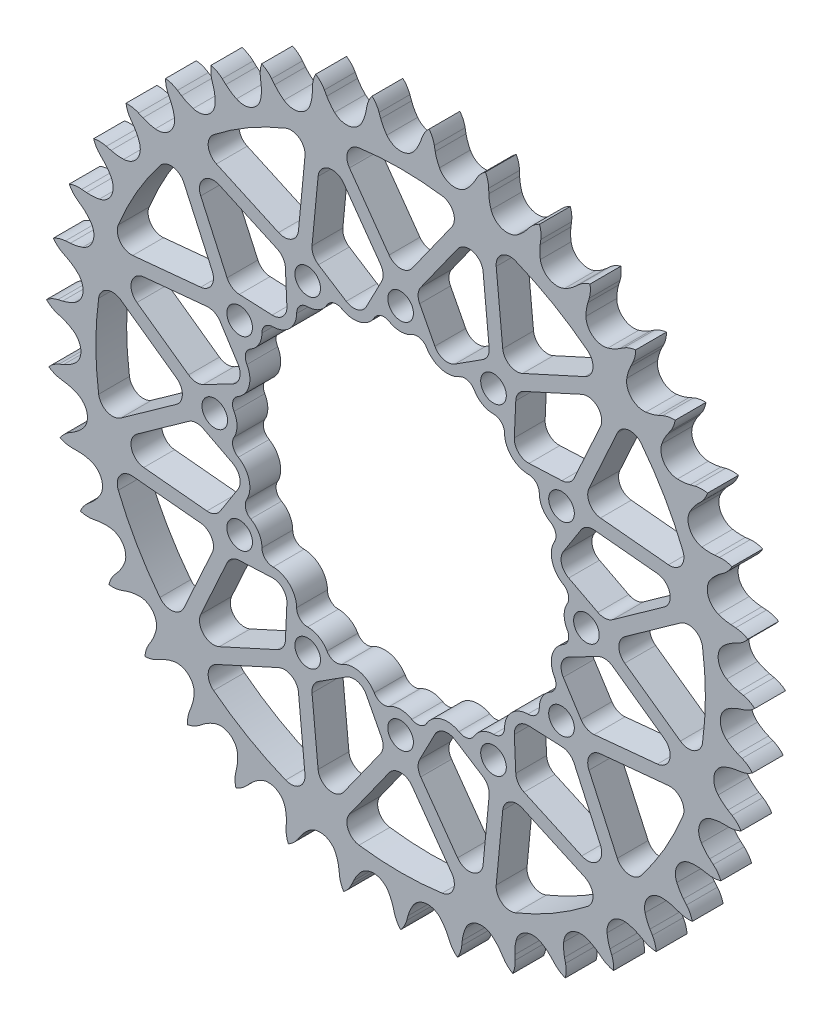
SolidWorks part; units mm, degrees
material "7075-T6 (SN)"
ref_plane "Front Plane" through (0, 0, 0) normal (0, 0, 1) x (1, 0, 0)
ref_plane "Top Plane" through (0, 0, 0) normal (0, 1, 0) x (1, 0, 0)
ref_plane "Right Plane" through (0, 0, 0) normal (1, 0, 0) x (0, 0, -1)
sketch "Work Sketch" plane through (0, 0, 0) normal (0, 0, 1) x (1, 0, 0)
  line L0 (0, 0) -> (0, 160.4542) construction
  line L1 (-112.0919, 78.9148) -> (87.2579, 78.9148) construction
  line L2 (5.102, 120.8822) -> (5.102, 112.9699) construction
  line L3 (-12.8497, 82.6953) -> (16.7256, 82.6953) construction
  line L4 (5.102, 82.6953) -> (-6.0879, 74.4036) construction
  line L5 (5.102, 82.6953) -> (-4.6505, 79.1506) construction
  line L6 (-4.6505, 79.1506) -> (-6.8863, 85.3019)
  line L7 (-11.5114, 78.0206) -> (-7.1525, 78.0206) construction
  line L8 (-11.0765, 124.7602) -> (-11.0765, 110.2345) construction
  line L9 (0, 0) -> (-3.4402, 42.6146) construction
  circle A0 centre (0, 0) radius 78.9148
  circle A1 centre (0, 78.9148) radius 4.0088
  arc A2 (-4.6505, 79.1506) -> (-3.2209, 76.5281) centre (5.0804, 82.7541) ccw
  circle A3 centre (-11.0765, 78.0206) radius 6.4254
  point P23 (-3.2209, 76.5281)
  dimension "D1" = 157.8295
  dimension "D8" = 10.3767
  dimension "D2" = 8.0177
  dimension "D3" = 5.102
  dimension "D4" = 3.7806
  dimension "D5" = 36.538
  dimension "D6" = 16.564
  dimension "D7" = 10.3767
  dimension "D9" = 0.8942
  dimension "D10" = 11.0765
  dimension "D11" = 4.615
sketch "Teeth Sketch" plane through (0, 0, 0) normal (0, 0, 1) x (1, 0, 0)
  line L0 (5.0376, 80.2155) -> (4.6505, 79.1506)
  line L1 (-7.4865, 92.7372) -> (-4.7839, 59.2593) construction
  line L2 (0, 0) -> (-10.9133, 132.3061) construction
  line L3 (7.8951, 79.9848) -> (8.1063, 78.8717)
  line L4 (16093.3137, -199351.4616) -> (-16096.7539, 199394.0762) construction
  line L5 (0, 146.3285) -> (0, 56.9858) construction
  line L6 (17.8398, 78.3686) -> (17.287, 77.3797)
  line L7 (0, -200000) -> (0, 200160.4542) construction
  line L8 (20.6234, 77.6826) -> (20.6533, 76.5499)
  line L9 (-4.6505, 79.1506) -> (-6.8863, 85.3019) construction
  line L10 (44.1616, 67.154) -> (43.8313, 66.0702)
  line L11 (-5.0376, 80.2155) -> (-4.6505, 79.1506)
  line L12 (30.18, 74.4921) -> (29.4757, 73.6046)
  line L13 (32.8175, 73.3684) -> (32.6653, 72.2456)
  line L14 (41.7385, 68.6862) -> (40.901, 67.9232)
  line L15 (52.2161, 61.1014) -> (51.267, 60.4826)
  line L16 (54.362, 59.2003) -> (53.8621, 58.1836)
  line L17 (61.3413, 51.9341) -> (60.3052, 51.4756)
  line L18 (63.1544, 49.7134) -> (62.4979, 48.79)
  line L19 (68.8777, 41.4218) -> (67.7815, 41.1354)
  line L20 (70.3112, 38.939) -> (69.515, 38.1328)
  line L21 (74.6303, 29.8366) -> (73.5023, 29.7298)
  line L22 (75.6469, 27.156) -> (74.7318, 26.488)
  line L23 (78.45, 17.4787) -> (77.3195, 17.5542)
  line L24 (79.0234, 14.6698) -> (78.013, 14.1572)
  line L25 (80.2378, 4.6681) -> (79.1341, 4.9239)
  line L26 (80.3533, 1.8035) -> (79.2737, 1.4597)
  line L27 (79.9476, -8.2634) -> (78.8992, -7.8338)
  line L28 (79.602, -11.1094) -> (78.4813, -11.2756)
  line L29 (77.5867, -20.9809) -> (76.6208, -20.3887)
  line L30 (76.7891, -23.7346) -> (75.6562, -23.7189)
  line L31 (73.2164, -33.155) -> (72.358, -32.4155)
  line L32 (71.9874, -35.7451) -> (70.8717, -35.5478)
  line L33 (66.9499, -44.4704) -> (66.2212, -43.6028)
  line L34 (65.3213, -46.8298) -> (64.2517, -46.4561)
  line L35 (58.9493, -54.634) -> (58.3693, -53.6608)
  line L36 (56.9634, -56.7016) -> (55.9676, -56.1612)
  line L37 (49.422, -63.3827) -> (49.0056, -62.329)
  line L38 (47.1301, -65.1049) -> (46.2339, -64.4118)
  line L39 (38.6147, -70.4897) -> (38.3727, -69.3829)
  line L40 (36.0763, -71.822) -> (35.3028, -70.9941)
  line L41 (26.8073, -75.7712) -> (26.746, -74.6398)
  line L42 (24.088, -76.679) -> (23.4574, -75.7377)
  line L43 (14.3056, -79.0901) -> (14.4266, -77.9636)
  line L44 (11.4759, -79.55) -> (11.0044, -78.5198)
  line L45 (1.4334, -80.3607) -> (1.7335, -79.2682)
  line L46 (-1.4334, -80.3607) -> (-1.7335, -79.2682)
  line L47 (-11.4759, -79.55) -> (-11.0044, -78.5198)
  line L48 (-14.3056, -79.0901) -> (-14.4266, -77.9636)
  line L49 (-24.088, -76.679) -> (-23.4574, -75.7377)
  line L50 (-26.8073, -75.7712) -> (-26.746, -74.6398)
  line L51 (-36.0763, -71.822) -> (-35.3028, -70.9941)
  line L52 (-38.6147, -70.4897) -> (-38.3727, -69.3829)
  line L53 (-47.1301, -65.1049) -> (-46.2339, -64.4118)
  line L54 (-49.422, -63.3827) -> (-49.0056, -62.329)
  line L55 (-56.9634, -56.7016) -> (-55.9676, -56.1612)
  line L56 (-58.9493, -54.634) -> (-58.3693, -53.6608)
  line L57 (-65.3213, -46.8298) -> (-64.2517, -46.4561)
  line L58 (-66.9499, -44.4704) -> (-66.2212, -43.6028)
  line L59 (-71.9874, -35.7451) -> (-70.8717, -35.5478)
  line L60 (-73.2164, -33.155) -> (-72.358, -32.4155)
  line L61 (-76.7891, -23.7346) -> (-75.6562, -23.7189)
  line L62 (-77.5867, -20.9809) -> (-76.6208, -20.3887)
  line L63 (-79.602, -11.1094) -> (-78.4813, -11.2756)
  line L64 (-79.9476, -8.2634) -> (-78.8992, -7.8338)
  line L65 (-80.3533, 1.8035) -> (-79.2737, 1.4597)
  line L66 (-80.2378, 4.6681) -> (-79.1341, 4.9239)
  line L67 (-79.0234, 14.6698) -> (-78.013, 14.1572)
  line L68 (-78.45, 17.4787) -> (-77.3195, 17.5542)
  line L69 (-75.6469, 27.156) -> (-74.7318, 26.488)
  line L70 (-74.6303, 29.8366) -> (-73.5023, 29.7298)
  line L71 (-70.3112, 38.939) -> (-69.515, 38.1328)
  line L72 (-68.8777, 41.4218) -> (-67.7815, 41.1354)
  line L73 (-63.1544, 49.7134) -> (-62.4979, 48.79)
  line L74 (-61.3413, 51.9341) -> (-60.3052, 51.4756)
  line L75 (-54.362, 59.2003) -> (-53.8621, 58.1836)
  line L76 (-52.2161, 61.1014) -> (-51.267, 60.4826)
  line L77 (-44.1616, 67.154) -> (-43.8313, 66.0702)
  line L78 (-41.7385, 68.6862) -> (-40.901, 67.9232)
  line L79 (-32.8175, 73.3684) -> (-32.6653, 72.2456)
  line L80 (-30.18, 74.4921) -> (-29.4757, 73.6046)
  line L81 (-20.6234, 77.6826) -> (-20.6533, 76.5499)
  line L82 (-17.8398, 78.3686) -> (-17.287, 77.3797)
  line L83 (-7.8951, 79.9848) -> (-8.1063, 78.8717)
  arc A0 (-6.8336, 82.8459) -> (-5.0376, 80.2155) centre (-11.0765, 78.0206) cw
  circle A1 centre (-11.0765, 78.0206) radius 6.4254 construction
  arc A2 (-3.2209, 76.5281) -> (-4.6505, 79.1506) centre (5.0804, 82.7541) cw
  arc A3 (-4.6505, 79.1506) -> (-3.2209, 76.5281) centre (5.0804, 82.7541) ccw construction
  circle A4 centre (0, 78.9148) radius 4.0088 construction
  arc A5 (-3.2209, 76.5281) -> (3.2209, 76.5281) centre (0, 78.9148) ccw
  arc A6 (3.2209, 76.5281) -> (4.6505, 79.1506) centre (-5.0804, 82.7541) ccw
  arc A7 (6.8336, 82.8459) -> (5.0376, 80.2155) centre (11.0765, 78.0206) ccw
  arc A8 (6.5443, 82.8692) -> (7.8951, 79.9848) centre (1.5824, 78.787) cw
  arc A9 (9.0967, 76.0537) -> (8.1063, 78.8717) centre (18.2893, 80.8676) cw
  arc A10 (9.0967, 76.0537) -> (15.4552, 75.0204) centre (12.6588, 77.8928) ccw
  arc A11 (15.4552, 75.0204) -> (17.287, 77.3797) centre (8.2601, 82.4975) ccw
  arc A12 (20.0345, 80.6769) -> (17.8398, 78.3686) centre (23.4484, 75.2334) ccw
  arc A13 (19.7528, 80.7463) -> (20.6234, 77.6826) centre (14.2002, 77.5129) cw
  arc A14 (21.1788, 73.6096) -> (20.6533, 76.5499) centre (31.0245, 76.8865) cw
  arc A15 (21.1788, 73.6096) -> (27.2892, 71.5697) centre (24.9898, 74.8535) ccw
  arc A16 (27.2892, 71.5697) -> (29.4757, 73.6046) centre (21.3867, 80.1041) ccw
  arc A17 (32.7165, 76.4184) -> (30.18, 74.4921) centre (35.2131, 70.4978) ccw
  arc A18 (32.4496, 76.5321) -> (32.8175, 73.3684) centre (26.4502, 74.2313) cw
  arc A19 (32.7124, 69.2591) -> (32.6653, 72.2456) centre (42.9562, 70.9142) cw
  arc A20 (32.7124, 69.2591) -> (38.4163, 66.2654) centre (36.6735, 69.8756) ccw
  arc A21 (38.4163, 66.2654) -> (40.901, 67.9232) centre (33.9593, 75.6361) ccw
  arc A22 (44.5512, 70.1807) -> (41.7385, 68.6862) centre (46.0657, 63.9363) ccw
  arc A23 (44.306, 70.3358) -> (44.1616, 67.154) centre (38.0153, 69.0271) cw
  arc A24 (43.3987, 63.1147) -> (43.8313, 66.0702) centre (53.7754, 63.1052) cw
  arc A25 (43.3987, 63.1147) -> (48.5486, 59.2448) centre (47.4074, 63.0878) ccw
  arc A26 (48.5486, 59.2448) -> (51.267, 60.4826) centre (45.6524, 69.2092) ccw
  arc A27 (55.2321, 62.1253) -> (52.2161, 61.1014) centre (55.7253, 55.7189) ccw
  arc A28 (55.0149, 62.3178) -> (54.362, 59.2003) centre (48.5957, 62.0351) cw
  arc A29 (52.961, 55.3358) -> (53.8621, 58.1836) centre (63.2018, 53.6618) cw
  arc A30 (52.961, 55.3358) -> (57.4234, 50.6899) centre (56.9135, 54.6662) ccw
  arc A31 (57.4234, 50.6899) -> (60.3052, 51.4756) centre (56.1632, 60.9898) ccw
  arc A32 (64.4824, 52.461) -> (61.3413, 51.9341) centre (63.9416, 46.0584) ccw
  arc A33 (64.2989, 52.6858) -> (63.1544, 49.7134) centre (57.9175, 53.4365) cw
  arc A34 (61.1517, 46.1237) -> (62.4979, 48.79) centre (70.9913, 42.8287) cw
  arc A35 (61.1517, 46.1237) -> (64.811, 40.8221) centre (64.9456, 44.8287) ccw
  arc A36 (64.811, 40.8221) -> (67.7815, 41.1354) centre (65.2193, 51.1908) ccw
  arc A37 (72.0627, 41.4379) -> (68.8777, 41.4218) centre (70.5018, 35.205) ccw
  arc A38 (71.9177, 41.6892) -> (70.3112, 38.939) centre (65.7393, 43.4539) cw
  arc A39 (67.7585, 35.717) -> (69.515, 38.1328) centre (76.9422, 30.8862) cw
  arc A40 (67.7585, 35.717) -> (70.5201, 29.8971) centre (71.2956, 33.8302) ccw
  arc A41 (70.5201, 29.8971) -> (73.5023, 29.7298) centre (72.5864, 40.0659) ccw
  arc A42 (77.7767, 29.3416) -> (74.6303, 29.8366) centre (75.2361, 23.4398) ccw
  arc A43 (77.6738, 29.6129) -> (75.6469, 27.156) centre (71.8585, 32.3458) cw
  arc A44 (72.6105, 24.3852) -> (74.7318, 26.488) centre (80.9003, 18.1439) cw
  arc A45 (72.6105, 24.3852) -> (74.4027, 18.1977) centre (75.7991, 21.9555) ccw
  arc A46 (74.4027, 18.1977) -> (77.3195, 17.5542) centre (78.0734, 27.9034) ccw
  arc A47 (81.4762, 16.4854) -> (78.45, 17.4787) centre (78.0218, 11.0675) ccw
  arc A48 (81.4182, 16.7697) -> (79.0234, 14.6698) centre (76.1166, 20.4) cw
  arc A49 (75.5818, 12.4219) -> (78.013, 14.1572) centre (82.7631, 4.9316) cw
  arc A50 (75.5818, 12.4219) -> (76.3583, 6.027) centre (78.3394, 9.5121) ccw
  arc A51 (76.3583, 6.027) -> (79.1341, 4.9239) centre (81.5384, 15.0182) ccw
  arc A52 (83.0656, 3.2022) -> (80.2378, 4.6681) centre (78.7868, -1.5914) ccw
  arc A53 (83.0539, 3.4922) -> (80.3533, 1.8035) centre (78.4033, 7.9259) cw
  arc A54 (76.5957, 0.1368) -> (79.2737, 1.4597) centre (82.4825, -8.4084) cw
  arc A55 (76.5957, 0.1368) -> (76.3363, -6.2998) centre (78.8508, -3.1776) ccw
  arc A56 (76.3363, -6.2998) -> (78.8992, -7.8338) centre (82.8916, 1.7441) ccw
  arc A57 (82.5035, -10.1639) -> (79.9476, -8.2634) centre (77.5113, -14.2091) ccw
  arc A58 (82.5385, -9.8758) -> (79.602, -11.1094) centre (78.6594, -4.7535) cw
  arc A59 (75.6257, -12.1517) -> (78.4813, -11.2756) centre (80.0655, -21.5307) cw
  arc A60 (75.6257, -12.1517) -> (74.3372, -18.4634) centre (77.3199, -15.785) ccw
  arc A61 (74.3372, -18.4634) -> (76.6208, -20.3887) centre (82.0979, -11.5753) ccw
  arc A62 (79.8047, -23.2668) -> (77.5867, -20.9809) centre (74.2283, -26.4587) ccw
  arc A63 (79.8855, -22.9881) -> (76.7891, -23.7346) centre (76.8783, -17.3098) cw
  arc A64 (72.6971, -24.1256) -> (75.6562, -23.7189) centre (75.5749, -34.0953) cw
  arc A65 (72.6971, -24.1256) -> (70.4128, -30.1488) centre (73.7866, -27.9836) ccw
  arc A66 (70.4128, -30.1488) -> (72.358, -32.4155) centre (79.178, -24.5948) ccw
  arc A67 (75.039, -35.7671) -> (73.2164, -33.155) centre (69.0227, -38.0232) ccw
  arc A68 (75.1634, -35.5049) -> (71.9874, -35.7451) centre (73.106, -29.4178) cw
  arc A69 (67.8857, -35.4746) -> (70.8717, -35.5478) centre (69.127, -45.7768) cw
  arc A70 (67.8857, -35.4746) -> (64.6648, -41.0534) centre (68.3422, -39.4574) ccw
  arc A71 (64.6648, -41.0534) -> (66.2212, -43.6028) centre (74.2074, -36.9773) ccw
  arc A72 (68.3299, -47.341) -> (66.9499, -44.4704) centre (62.0296, -48.6028) ccw
  arc A73 (68.4947, -47.1022) -> (65.3213, -46.8298) centre (67.4404, -40.7639) cw
  arc A74 (61.3161, -45.9049) -> (64.2517, -46.4561) centre (60.8887, -56.2728) cw
  arc A75 (61.3161, -45.9049) -> (57.2419, -50.8948) centre (61.1278, -49.9093) ccw
  arc A76 (57.2419, -50.8948) -> (58.3693, -53.6608) centre (67.3148, -48.4022) ccw
  arc A77 (59.851, -57.6888) -> (58.9493, -54.634) centre (53.4299, -57.9236) ccw
  arc A78 (60.052, -57.4796) -> (56.9634, -56.7016) centre (60.0281, -51.0542) cw
  arc A79 (53.1584, -55.1462) -> (55.9676, -56.1612) centre (51.0734, -65.3113) cw
  arc A80 (53.1584, -55.1462) -> (48.3366, -59.4179) centre (52.3302, -59.0685) ccw
  arc A81 (48.3366, -59.4179) -> (49.0056, -62.329) centre (58.6789, -58.5735) ccw
  arc A82 (49.822, -66.5425) -> (49.422, -63.3827) centre (43.4464, -65.7443) ccw
  arc A83 (50.054, -66.3682) -> (47.1301, -65.1049) centre (51.0611, -60.0222) cw
  arc A84 (43.6239, -62.9593) -> (46.2339, -64.4118) centre (39.9354, -72.6583) cw
  arc A85 (43.6239, -62.9593) -> (38.1793, -66.4022) centre (42.1772, -66.698) ccw
  arc A86 (38.1793, -66.4022) -> (38.3727, -69.3829) centre (48.5231, -67.2277) ccw
  arc A87 (38.5026, -73.6728) -> (38.6147, -70.4897) centre (32.3376, -71.8622) ccw
  arc A88 (38.7596, -73.538) -> (36.0763, -71.822) centre (40.7716, -67.4357) cw
  arc A89 (32.9596, -69.1417) -> (35.3028, -70.9941) centre (27.763, -78.1234) cw
  arc A90 (32.9596, -69.1417) -> (27.0333, -71.6667) centre (30.932, -72.6) ccw
  arc A91 (27.0333, -71.6667) -> (26.746, -74.6398) centre (37.1107, -74.1408) ccw
  arc A92 (26.1861, -78.8951) -> (26.8073, -75.7712) centre (20.3913, -76.1189) ccw
  arc A93 (26.4613, -78.8032) -> (24.088, -76.679) centre (29.4261, -73.1027) cw
  arc A94 (21.4417, -73.5335) -> (23.4574, -75.7377) centre (14.8716, -81.5653) cw
  arc A95 (21.4417, -73.5335) -> (15.187, -75.0751) centre (18.8855, -76.6216) ccw
  arc A96 (15.187, -75.0751) -> (14.4266, -77.9636) centre (24.7371, -79.1336) ccw
  arc A97 (13.1913, -82.0739) -> (14.3056, -79.0901) centre (7.9169, -78.4042) ccw
  arc A98 (13.4777, -82.0274) -> (11.4759, -79.55) centre (17.3186, -76.8763) cw
  arc A99 (9.3684, -76.0207) -> (11.0044, -78.5198) centre (1.595, -82.8946) cw
  arc A100 (9.3684, -76.0207) -> (2.9475, -76.5391) centre (6.35, -78.6589) ccw
  arc A101 (2.9475, -76.5391) -> (1.7335, -79.2682) centre (11.7228, -82.077) ccw
  arc A102 (-0.1451, -83.1271) -> (1.4334, -80.3607) centre (-4.7625, -78.6589) ccw
  arc A103 (0.1451, -83.1271) -> (-1.4334, -80.3607) centre (4.7625, -78.6589) cw
  arc A104 (-2.9475, -76.5391) -> (-1.7335, -79.2682) centre (-11.7228, -82.077) cw
  arc A105 (-2.9475, -76.5391) -> (-9.3684, -76.0207) centre (-6.35, -78.6589) ccw
  arc A106 (-9.3684, -76.0207) -> (-11.0044, -78.5198) centre (-1.595, -82.8946) ccw
  arc A107 (-13.4777, -82.0274) -> (-11.4759, -79.55) centre (-17.3186, -76.8763) ccw
  arc A108 (-13.1913, -82.0739) -> (-14.3056, -79.0901) centre (-7.9169, -78.4042) cw
  arc A109 (-15.187, -75.0751) -> (-14.4266, -77.9636) centre (-24.7371, -79.1336) cw
  arc A110 (-15.187, -75.0751) -> (-21.4417, -73.5335) centre (-18.8855, -76.6216) ccw
  arc A111 (-21.4417, -73.5335) -> (-23.4574, -75.7377) centre (-14.8716, -81.5653) ccw
  arc A112 (-26.4613, -78.8032) -> (-24.088, -76.679) centre (-29.4261, -73.1027) ccw
  arc A113 (-26.1861, -78.8951) -> (-26.8073, -75.7712) centre (-20.3913, -76.1189) cw
  arc A114 (-27.0333, -71.6667) -> (-26.746, -74.6398) centre (-37.1107, -74.1408) cw
  arc A115 (-27.0333, -71.6667) -> (-32.9596, -69.1417) centre (-30.932, -72.6) ccw
  arc A116 (-32.9596, -69.1417) -> (-35.3028, -70.9941) centre (-27.763, -78.1234) ccw
  arc A117 (-38.7596, -73.538) -> (-36.0763, -71.822) centre (-40.7716, -67.4357) ccw
  arc A118 (-38.5026, -73.6728) -> (-38.6147, -70.4897) centre (-32.3376, -71.8622) cw
  arc A119 (-38.1793, -66.4022) -> (-38.3727, -69.3829) centre (-48.5231, -67.2277) cw
  arc A120 (-38.1793, -66.4022) -> (-43.6239, -62.9593) centre (-42.1772, -66.698) ccw
  arc A121 (-43.6239, -62.9593) -> (-46.2339, -64.4118) centre (-39.9354, -72.6583) ccw
  arc A122 (-50.054, -66.3682) -> (-47.1301, -65.1049) centre (-51.0611, -60.0222) ccw
  arc A123 (-49.822, -66.5425) -> (-49.422, -63.3827) centre (-43.4464, -65.7443) cw
  arc A124 (-48.3366, -59.4179) -> (-49.0056, -62.329) centre (-58.6789, -58.5735) cw
  arc A125 (-48.3366, -59.4179) -> (-53.1584, -55.1462) centre (-52.3302, -59.0685) ccw
  arc A126 (-53.1584, -55.1462) -> (-55.9676, -56.1612) centre (-51.0734, -65.3113) ccw
  arc A127 (-60.052, -57.4796) -> (-56.9634, -56.7016) centre (-60.0281, -51.0542) ccw
  arc A128 (-59.851, -57.6888) -> (-58.9493, -54.634) centre (-53.4299, -57.9236) cw
  arc A129 (-57.2419, -50.8948) -> (-58.3693, -53.6608) centre (-67.3148, -48.4022) cw
  arc A130 (-57.2419, -50.8948) -> (-61.3161, -45.9049) centre (-61.1278, -49.9093) ccw
  arc A131 (-61.3161, -45.9049) -> (-64.2517, -46.4561) centre (-60.8887, -56.2728) ccw
  arc A132 (-68.4947, -47.1022) -> (-65.3213, -46.8298) centre (-67.4404, -40.7639) ccw
  arc A133 (-68.3299, -47.341) -> (-66.9499, -44.4704) centre (-62.0296, -48.6028) cw
  arc A134 (-64.6648, -41.0534) -> (-66.2212, -43.6028) centre (-74.2074, -36.9773) cw
  arc A135 (-64.6648, -41.0534) -> (-67.8857, -35.4746) centre (-68.3422, -39.4574) ccw
  arc A136 (-67.8857, -35.4746) -> (-70.8717, -35.5478) centre (-69.127, -45.7768) ccw
  arc A137 (-75.1634, -35.5049) -> (-71.9874, -35.7451) centre (-73.106, -29.4178) ccw
  arc A138 (-75.039, -35.7671) -> (-73.2164, -33.155) centre (-69.0227, -38.0232) cw
  arc A139 (-70.4128, -30.1488) -> (-72.358, -32.4155) centre (-79.178, -24.5948) cw
  arc A140 (-70.4128, -30.1488) -> (-72.6971, -24.1256) centre (-73.7866, -27.9836) ccw
  arc A141 (-72.6971, -24.1256) -> (-75.6562, -23.7189) centre (-75.5749, -34.0953) ccw
  arc A142 (-79.8855, -22.9881) -> (-76.7891, -23.7346) centre (-76.8783, -17.3098) ccw
  arc A143 (-79.8047, -23.2668) -> (-77.5867, -20.9809) centre (-74.2283, -26.4587) cw
  arc A144 (-74.3372, -18.4634) -> (-76.6208, -20.3887) centre (-82.0979, -11.5753) cw
  arc A145 (-74.3372, -18.4634) -> (-75.6257, -12.1517) centre (-77.3199, -15.785) ccw
  arc A146 (-75.6257, -12.1517) -> (-78.4813, -11.2756) centre (-80.0655, -21.5307) ccw
  arc A147 (-82.5385, -9.8758) -> (-79.602, -11.1094) centre (-78.6594, -4.7535) ccw
  arc A148 (-82.5035, -10.1639) -> (-79.9476, -8.2634) centre (-77.5113, -14.2091) cw
  arc A149 (-76.3363, -6.2998) -> (-78.8992, -7.8338) centre (-82.8916, 1.7441) cw
  arc A150 (-76.3363, -6.2998) -> (-76.5957, 0.1368) centre (-78.8508, -3.1776) ccw
  arc A151 (-76.5957, 0.1368) -> (-79.2737, 1.4597) centre (-82.4825, -8.4084) ccw
  arc A152 (-83.0539, 3.4922) -> (-80.3533, 1.8035) centre (-78.4033, 7.9259) ccw
  arc A153 (-83.0656, 3.2022) -> (-80.2378, 4.6681) centre (-78.7868, -1.5914) cw
  arc A154 (-76.3583, 6.027) -> (-79.1341, 4.9239) centre (-81.5384, 15.0182) cw
  arc A155 (-76.3583, 6.027) -> (-75.5818, 12.4219) centre (-78.3394, 9.5121) ccw
  arc A156 (-75.5818, 12.4219) -> (-78.013, 14.1572) centre (-82.7631, 4.9316) ccw
  arc A157 (-81.4182, 16.7697) -> (-79.0234, 14.6698) centre (-76.1166, 20.4) ccw
  arc A158 (-81.4762, 16.4854) -> (-78.45, 17.4787) centre (-78.0218, 11.0675) cw
  arc A159 (-74.4027, 18.1977) -> (-77.3195, 17.5542) centre (-78.0734, 27.9034) cw
  arc A160 (-74.4027, 18.1977) -> (-72.6105, 24.3852) centre (-75.7991, 21.9555) ccw
  arc A161 (-72.6105, 24.3852) -> (-74.7318, 26.488) centre (-80.9003, 18.1439) ccw
  arc A162 (-77.6738, 29.6129) -> (-75.6469, 27.156) centre (-71.8585, 32.3458) ccw
  arc A163 (-77.7767, 29.3416) -> (-74.6303, 29.8366) centre (-75.2361, 23.4398) cw
  arc A164 (-70.5201, 29.8971) -> (-73.5023, 29.7298) centre (-72.5864, 40.0659) cw
  arc A165 (-70.5201, 29.8971) -> (-67.7585, 35.717) centre (-71.2956, 33.8302) ccw
  arc A166 (-67.7585, 35.717) -> (-69.515, 38.1328) centre (-76.9422, 30.8862) ccw
  arc A167 (-71.9177, 41.6892) -> (-70.3112, 38.939) centre (-65.7393, 43.4539) ccw
  arc A168 (-72.0627, 41.4379) -> (-68.8777, 41.4218) centre (-70.5018, 35.205) cw
  arc A169 (-64.811, 40.8221) -> (-67.7815, 41.1354) centre (-65.2193, 51.1908) cw
  arc A170 (-64.811, 40.8221) -> (-61.1517, 46.1237) centre (-64.9456, 44.8287) ccw
  arc A171 (-61.1517, 46.1237) -> (-62.4979, 48.79) centre (-70.9913, 42.8287) ccw
  arc A172 (-64.2989, 52.6858) -> (-63.1544, 49.7134) centre (-57.9175, 53.4365) ccw
  arc A173 (-64.4824, 52.461) -> (-61.3413, 51.9341) centre (-63.9416, 46.0584) cw
  arc A174 (-57.4234, 50.6899) -> (-60.3052, 51.4756) centre (-56.1632, 60.9898) cw
  arc A175 (-57.4234, 50.6899) -> (-52.961, 55.3358) centre (-56.9135, 54.6662) ccw
  arc A176 (-52.961, 55.3358) -> (-53.8621, 58.1836) centre (-63.2018, 53.6618) ccw
  arc A177 (-55.0149, 62.3178) -> (-54.362, 59.2003) centre (-48.5957, 62.0351) ccw
  arc A178 (-55.2321, 62.1253) -> (-52.2161, 61.1014) centre (-55.7253, 55.7189) cw
  arc A179 (-48.5486, 59.2448) -> (-51.267, 60.4826) centre (-45.6524, 69.2092) cw
  arc A180 (-48.5486, 59.2448) -> (-43.3987, 63.1147) centre (-47.4074, 63.0878) ccw
  arc A181 (-43.3987, 63.1147) -> (-43.8313, 66.0702) centre (-53.7754, 63.1052) ccw
  arc A182 (-44.306, 70.3358) -> (-44.1616, 67.154) centre (-38.0153, 69.0271) ccw
  arc A183 (-44.5512, 70.1807) -> (-41.7385, 68.6862) centre (-46.0657, 63.9363) cw
  arc A184 (-38.4163, 66.2654) -> (-40.901, 67.9232) centre (-33.9593, 75.6361) cw
  arc A185 (-38.4163, 66.2654) -> (-32.7124, 69.2591) centre (-36.6735, 69.8756) ccw
  arc A186 (-32.7124, 69.2591) -> (-32.6653, 72.2456) centre (-42.9562, 70.9142) ccw
  arc A187 (-32.4496, 76.5321) -> (-32.8175, 73.3684) centre (-26.4502, 74.2313) ccw
  arc A188 (-32.7165, 76.4184) -> (-30.18, 74.4921) centre (-35.2131, 70.4978) cw
  arc A189 (-27.2892, 71.5697) -> (-29.4757, 73.6046) centre (-21.3867, 80.1041) cw
  arc A190 (-27.2892, 71.5697) -> (-21.1788, 73.6096) centre (-24.9898, 74.8535) ccw
  arc A191 (-21.1788, 73.6096) -> (-20.6533, 76.5499) centre (-31.0245, 76.8865) ccw
  arc A192 (-19.7528, 80.7463) -> (-20.6234, 77.6826) centre (-14.2002, 77.5129) ccw
  arc A193 (-20.0345, 80.6769) -> (-17.8398, 78.3686) centre (-23.4484, 75.2334) cw
  arc A194 (-15.4552, 75.0204) -> (-17.287, 77.3797) centre (-8.2601, 82.4975) cw
  arc A195 (-15.4552, 75.0204) -> (-9.0967, 76.0537) centre (-12.6588, 77.8928) ccw
  arc A196 (-9.0967, 76.0537) -> (-8.1063, 78.8717) centre (-18.2893, 80.8676) ccw
  arc A197 (-6.5443, 82.8692) -> (-7.8951, 79.9848) centre (-1.5824, 78.787) ccw
  point P77 (0, 0)
  dimension "D1" = 4.615
  dimension "D2" = 4.715
  dimension "D3" = 39
extrude "Extrusion" add sketch "Teeth Sketch" along normal blind 7.2136 contours A0 region at (0, 0, 0)
sketch "Sketch1" plane through (0, 0, 0) normal (0, 0, -1) x (-1, 0, 0)
  circle A0 centre (0, 0) radius 78.9443
  circle A1 centre (0, 0) radius 35.7643
  dimension "D1" = 43.18
extrude "Cut-Extrude" cut sketch "Sketch1" against normal through all both and the other way through all contours A1
ref_axis "Axis1" [suppressed] through (0, 0, 7.2136) along (0, 0, -1)
ref_plane "Sprocket Center Plane" through (0, 0, 3.6068) normal (0, 0, 1) x (1, 0, 0)
sketch "Pitch Circle" plane through (0, 0, 3.6068) normal (0, 0, -1) x (-1, 0, 0)
  circle A0 centre (0, 0) radius 82.9531 construction
  dimension "D1" = 165.9063
sketch "Chain Pitch Circle" plane through (0, 0, 0) normal (0, 0, -1) x (-1, 0, 0)
  circle A0 centre (0, 0) radius 82.9531 construction
  dimension "D1" = 165.9063
ref_plane "Center Plane" through (0, 0, 3.6068) normal (0, 0, 1) x (1, 0, 0)
hole_wizard "Ø6.0mm Dowel Hole1" positions "Sketch7" profile "Sketch8" hole size "Ø6.0" standard "ANSI Metric" end condition through all
sketch "Sketch7" plane through (0, 0, 7.2136) normal (0, 0, 1) x (1, 0, 0)
  point P0 (-43.5, 0)
  dimension "D1" = 43.5
sketch "Sketch8" plane through (-43.5, 0, 7.2136) normal (1, 0, 0) x (0, -1, 0)
  line L0 (0, 0) -> (0, 7.2136)
  line L1 (0, 7.2136) -> (3, 7.2136)
  line L2 (3, 7.2136) -> (3, 0)
  line L5 (3, 0) -> (0, 0)
  line L11 (0, -6.35) -> (0, 107.95) construction
  dimension "Thru Hole Dia." = 6
  dimension "Thru Hole Depth" = 7.2136
pattern_circular "CirPattern1" count 12 over 360 about axis through (0, 0, 7.2136) along (0, 0, -1) of "Ø6.0mm Dowel Hole1" reverse direction yes
ref_plane "Plane1" through (0, 0, 3.6068) normal (0, 0, -1) x (-1, 0, 0)
sketch "Sketch9" plane through (0, 0, 0) normal (0, 0, 1) x (1, 0, 0)
  line L0 (-43.5, 0) -> (-71.3499, 0) construction
  line L1 (-69.7539, 15.0068) -> (-48.707, 0)
  line L2 (-69.7539, -15.0068) -> (-48.707, 0)
  line L11 (-43.5, 0) -> (-37.6721, 21.75) construction
  line L13 (-68.9187, 18.4667) -> (-36.1404, 9.6838) construction
  line L18 (-43.3252, 20.9264) -> (-36.1404, 9.6838)
  line L19 (-47.9839, 3.5399) -> (-36.1404, 9.6838)
  line L20 (-43.3252, 20.9264) -> (-68.9187, 18.4667)
  line L21 (-47.9839, 3.5399) -> (-68.9187, 18.4667)
  circle A0 centre (0, 0) radius 74.9059 construction
  arc A1 (-57.4234, 50.6899) -> (-52.961, 55.3358) centre (-56.9135, 54.6662) ccw construction
  circle A2 centre (-43.5, 0) radius 3 construction
  circle A3 centre (-43.5, 0) radius 5.207
  circle A4 centre (-37.6721, 21.75) radius 3 construction
  circle A6 centre (-37.6721, 21.75) radius 5.207
  circle A196 centre (0, 0) radius 71.3499
  circle A197 centre (0, 0) radius 35.7643 construction
  circle A198 centre (0, 0) radius 35.7643
  circle A199 centre (0, 0) radius 37.4153 construction
  point P17 (-40.5861, 10.875)
  dimension "D1" = 3.556
  dimension "D2" = 1.651
  dimension "D3" = 10.414
  dimension "D4" = 3.302
extrude "Cut-Extrude2" cut sketch "Sketch9" along normal through all contours L1 A196 L2 | L21 L19 L18 L20 region at (-63.4426, 0, 0) region at (-50.2379, 13.4612, 0)
fillet "Fillet2" radius 3.302 7 edges at (-68.9187, 18.4667, 3.6068) (-36.1404, 9.6838, 3.6068) (-47.9839, 3.5399, 3.6068) (-43.3252, 20.9264, 3.6068) (-69.7539, -15.0068, 3.6068) (-48.707, 0, 3.6068) (-69.7539, 15.0068, 3.6068)
pattern_circular "CirPattern3" count 12 over 360 about axis through (0, 0, 7.2136) along (0, 0, -1) of "Cut-Extrude2", "Fillet2"
sketch "Sketch14" plane through (0, 0, 7.2136) normal (0, 0, 1) x (1, 0, 0)
  line L0 (-46.191, -4.47) -> (-39.3483, -8.0197) construction
  line L1 (-38.2956, 5.9905) -> (-37.9766, 6.1559)
  line L2 (-43.5, 0) -> (-38.293, 0) construction
  line L3 (-38.2956, -5.9905) -> (-37.9766, -6.1559)
  line L4 (-30.1697, 24.3357) -> (-29.8108, 24.3195)
  line L5 (-36.1602, 13.9599) -> (-35.9667, 13.6571)
  line L6 (-13.9599, 36.1602) -> (-13.6571, 35.9667)
  line L7 (-24.3357, 30.1697) -> (-24.3195, 29.8108)
  line L8 (5.9905, 38.2956) -> (6.1559, 37.9766)
  line L9 (-5.9905, 38.2956) -> (-6.1559, 37.9766)
  line L10 (24.3357, 30.1697) -> (24.3195, 29.8108)
  line L11 (13.9599, 36.1602) -> (13.6571, 35.9667)
  line L12 (36.1602, 13.9599) -> (35.9667, 13.6571)
  line L13 (30.1697, 24.3357) -> (29.8108, 24.3195)
  line L14 (38.2956, -5.9905) -> (37.9766, -6.1559)
  line L15 (38.2956, 5.9905) -> (37.9766, 6.1559)
  line L16 (30.1697, -24.3357) -> (29.8108, -24.3195)
  line L17 (36.1602, -13.9599) -> (35.9667, -13.6571)
  line L18 (13.9599, -36.1602) -> (13.6571, -35.9667)
  line L19 (24.3357, -30.1697) -> (24.3195, -29.8108)
  line L20 (-5.9905, -38.2956) -> (-6.1559, -37.9766)
  line L21 (5.9905, -38.2956) -> (6.1559, -37.9766)
  line L22 (-24.3357, -30.1697) -> (-24.3195, -29.8108)
  line L23 (-13.9599, -36.1602) -> (-13.6571, -35.9667)
  line L24 (-36.1602, -13.9599) -> (-35.9667, -13.6571)
  line L25 (-30.1697, -24.3357) -> (-29.8108, -24.3195)
  arc A0 (-39.0014, -2.6222) -> (-39.0014, 2.6222) centre (-43.5, 0) ccw
  circle A1 centre (0, 0) radius 35.7643 construction
  arc A2 (-37.9766, -6.1559) -> (-39.0014, -2.6222) centre (-36.807, -3.9013) cw
  arc A3 (-38.2956, 5.9905) -> (-36.1602, 13.9599) centre (-40.8688, 10.9508) ccw
  arc A4 (-38.2956, 5.9905) -> (-36.1602, 13.9599) centre (-40.8688, 10.9508) ccw
  arc A5 (-37.9766, 6.1559) -> (-39.0014, 2.6222) centre (-36.807, 3.9013) ccw
  circle A6 centre (0, 0) radius 35.7643
  arc A7 (-30.1697, 24.3357) -> (-24.3357, 30.1697) centre (-29.918, 29.918) ccw
  arc A8 (-29.8108, 24.3195) -> (-32.4651, 21.7716) centre (-29.9252, 21.7821) ccw
  arc A9 (-35.0873, 17.2299) -> (-32.4651, 21.7716) centre (-37.6721, 21.75) ccw
  arc A10 (-35.9667, 13.6571) -> (-35.0873, 17.2299) centre (-33.8264, 15.0249) cw
  arc A11 (-13.9599, 36.1602) -> (-5.9905, 38.2956) centre (-10.9508, 40.8688) ccw
  arc A12 (-13.6571, 35.9667) -> (-17.2299, 35.0873) centre (-15.0249, 33.8264) ccw
  arc A13 (-21.7716, 32.4651) -> (-17.2299, 35.0873) centre (-21.75, 37.6721) ccw
  arc A14 (-24.3195, 29.8108) -> (-21.7716, 32.4651) centre (-21.7821, 29.9252) cw
  arc A15 (5.9905, 38.2956) -> (13.9599, 36.1602) centre (10.9508, 40.8688) ccw
  arc A16 (6.1559, 37.9766) -> (2.6222, 39.0014) centre (3.9013, 36.807) ccw
  arc A17 (-2.6222, 39.0014) -> (2.6222, 39.0014) centre (0, 43.5) ccw
  arc A18 (-6.1559, 37.9766) -> (-2.6222, 39.0014) centre (-3.9013, 36.807) cw
  arc A19 (24.3357, 30.1697) -> (30.1697, 24.3357) centre (29.918, 29.918) ccw
  arc A20 (24.3195, 29.8108) -> (21.7716, 32.4651) centre (21.7821, 29.9252) ccw
  arc A21 (17.2299, 35.0873) -> (21.7716, 32.4651) centre (21.75, 37.6721) ccw
  arc A22 (13.6571, 35.9667) -> (17.2299, 35.0873) centre (15.0249, 33.8264) cw
  arc A23 (36.1602, 13.9599) -> (38.2956, 5.9905) centre (40.8688, 10.9508) ccw
  arc A24 (35.9667, 13.6571) -> (35.0873, 17.2299) centre (33.8264, 15.0249) ccw
  arc A25 (32.4651, 21.7716) -> (35.0873, 17.2299) centre (37.6721, 21.75) ccw
  arc A26 (29.8108, 24.3195) -> (32.4651, 21.7716) centre (29.9252, 21.7821) cw
  arc A27 (38.2956, -5.9905) -> (36.1602, -13.9599) centre (40.8688, -10.9508) ccw
  arc A28 (37.9766, -6.1559) -> (39.0014, -2.6222) centre (36.807, -3.9013) ccw
  arc A29 (39.0014, 2.6222) -> (39.0014, -2.6222) centre (43.5, 0) ccw
  arc A30 (37.9766, 6.1559) -> (39.0014, 2.6222) centre (36.807, 3.9013) cw
  arc A31 (30.1697, -24.3357) -> (24.3357, -30.1697) centre (29.918, -29.918) ccw
  arc A32 (29.8108, -24.3195) -> (32.4651, -21.7716) centre (29.9252, -21.7821) ccw
  arc A33 (35.0873, -17.2299) -> (32.4651, -21.7716) centre (37.6721, -21.75) ccw
  arc A34 (35.9667, -13.6571) -> (35.0873, -17.2299) centre (33.8264, -15.0249) cw
  arc A35 (13.9599, -36.1602) -> (5.9905, -38.2956) centre (10.9508, -40.8688) ccw
  arc A36 (13.6571, -35.9667) -> (17.2299, -35.0873) centre (15.0249, -33.8264) ccw
  arc A37 (21.7716, -32.4651) -> (17.2299, -35.0873) centre (21.75, -37.6721) ccw
  arc A38 (24.3195, -29.8108) -> (21.7716, -32.4651) centre (21.7821, -29.9252) cw
  arc A39 (-5.9905, -38.2956) -> (-13.9599, -36.1602) centre (-10.9508, -40.8688) ccw
  arc A40 (-6.1559, -37.9766) -> (-2.6222, -39.0014) centre (-3.9013, -36.807) ccw
  arc A41 (2.6222, -39.0014) -> (-2.6222, -39.0014) centre (0, -43.5) ccw
  arc A42 (6.1559, -37.9766) -> (2.6222, -39.0014) centre (3.9013, -36.807) cw
  arc A43 (-24.3357, -30.1697) -> (-30.1697, -24.3357) centre (-29.918, -29.918) ccw
  arc A44 (-24.3195, -29.8108) -> (-21.7716, -32.4651) centre (-21.7821, -29.9252) ccw
  arc A45 (-17.2299, -35.0873) -> (-21.7716, -32.4651) centre (-21.75, -37.6721) ccw
  arc A46 (-13.6571, -35.9667) -> (-17.2299, -35.0873) centre (-15.0249, -33.8264) cw
  arc A47 (-36.1602, -13.9599) -> (-38.2956, -5.9905) centre (-40.8688, -10.9508) ccw
  arc A48 (-35.9667, -13.6571) -> (-35.0873, -17.2299) centre (-33.8264, -15.0249) ccw
  arc A49 (-32.4651, -21.7716) -> (-35.0873, -17.2299) centre (-37.6721, -21.75) ccw
  arc A50 (-29.8108, -24.3195) -> (-32.4651, -21.7716) centre (-29.9252, -21.7821) cw
  point P10 (-41.0188, -4.5778)
  point P16 (-41.0188, 4.5778)
  point P144 (0, 0)
  dimension "D2" = 2.54
  dimension "D1" = 2.286
  dimension "D3" = 12
extrude "Cut-Extrude7" cut sketch "Sketch14" against normal through all
equation "\"P\"= 0.500'//Chain Pitch"
equation "\"N\"= 39'//Number of Teeth"
equation "\"Dr\"= 5 / 16'//Roller Diameter"
equation "\"Ds\"= 1.0005 * \"Dr\" + 0.003'Seating Curve DIameter"
equation "\"R\"= \"Ds\" / 2"
equation "\"A\"= 35 + 60 / \"N\""
equation "\"B\"= 18 - 56 / \"N\""
equation "\"ac\"= 0.8 * \"Dr\""
equation "\"M\"= 0.8 * \"Dr\" * cos ( 35 + 60 / \"N\" )"
equation "\"T\"= 0.8 * \"Dr\" * sin ( 35 + 60 / \"N\" )"
equation "\"E\"= 1.3025 * \"Dr\" + 0.0015"
equation "\"Chordal Length of Arc xy\"= ( 2.605 * \"Dr\" + 0.003 ) * sin ( 9 - 28 / \"N\" )"
equation "\"yz\"= \"Dr\" * ( 1.4 * sin ( 17 - 64 / \"N\" ) - 0.8 * sin ( 18 - 56 / \"N\" ) )"
equation "\"ab\"= 1.4 * \"Dr\""
equation "\"W\"= 1.4 * \"Dr\" * cos ( 180 / \"N\" )"
equation "\"V\"= 1.4 * \"Dr\" * sin ( 180 / \"N\" )"
equation "\"F\"= \"Dr\" * ( 0.8 * cos ( 18 - 56 / \"N\" ) + 1.4 * cos ( 17 - 64 / \"N\" ) - 1.3025 )"
equation "\"H\"= sqr ( \"F\" ^ 2 - ( 1.4 * \"Dr\" - \"P\" / 2 ) ^ 2 )"
equation "\"S\"= \"P\" / 2 * cos ( 180 / \"N\" ) + \"H\" * sin ( 180 / \"N\" )"
equation "\"PD\"= \"P\" / ( sin ( 180 / \"N\" ) )"
equation "\"D1@Work Sketch\" = \"PD\""
equation "\"D3@Work Sketch\" = \"M\""
equation "\"D4@Work Sketch\" = \"T\""
equation "\"D5@Work Sketch\" = \"A\""
equation "\"D6@Work Sketch\" = \"B\""
equation "\"D7@Work Sketch\" = \"E\""
equation "\"D8@Work Sketch\" = \"E\""
equation "\"D9@Work Sketch\" = \"V\""
equation "\"D10@Work Sketch\" = \"W\""
equation "\"D2@Work Sketch\" = \"R\" * 2"
equation "\"D11@Work Sketch\" = 180 / \"N\""
equation "\"D2@Teeth Sketch\" = 180 / \"N\" + 0.1"
equation "\"D3@Teeth Sketch\" = \"N\""
equation "\"Edge Thickness\"=1.7"
equation "\"D1@Sketch1\"=\"Edge Thickness\""
equation "\"InnerRib\"=0.060000"
equation "\"ST\"= 0.284'//Sprocket Thickness"
